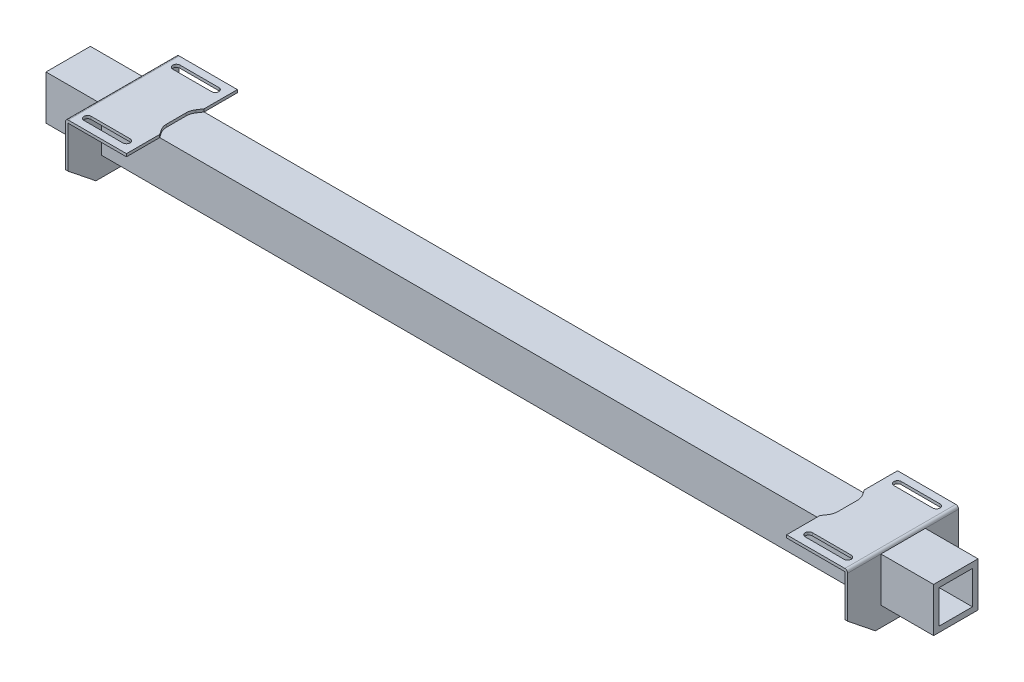
SolidWorks part; units mm, degrees
ref_plane "Front Plane" through (0, 0, 0) normal (0, 0, 1) x (1, 0, 0)
ref_plane "Top Plane" through (0, 0, 0) normal (0, 1, 0) x (1, 0, 0)
ref_plane "Right Plane" through (0, 0, 0) normal (1, 0, 0) x (0, 0, -1)
sketch "Sketch3" plane through (0, 0, 0) normal (1, 0, 0) x (0, 0, -1)
  line L1 (0, 0) -> (80, 0)
  line L2 (0, 0) -> (0, 80)
  line L3 (0, 80) -> (80, 80)
  line L4 (80, 0) -> (80, 80)
  line L5 (10, 70) -> (70, 70)
  line L6 (10, 70) -> (10, 10)
  line L7 (10, 10) -> (70, 10)
  line L8 (70, 70) -> (70, 10)
  dimension "D1" = 80
  dimension "D2" = 80
  dimension "D3" = 10
  dimension "D4" = 10
  dimension "D5" = 10
  dimension "D6" = 10
extrude "Boss-Extrude2" add sketch "Sketch3" along normal blind 1600
ref_plane "Plane1" through (1500, 0, 0) normal (1, 0, 0) x (0, 0, -1)
sketch "Sketch7" plane through (1500, 0, 0) normal (1, 0, 0) x (0, 0, -1)
  line L0 (-60, 85) -> (140, 85)
  line L1 (140, 85) -> (140, 5)
  line L2 (140, 5) -> (90, -35)
  line L3 (90, -35) -> (-10, -35)
  line L4 (-10, -35) -> (-60, 5)
  line L5 (-60, 5) -> (-60, 85)
  line L6 (80, 80) -> (0, 80) construction
  line L7 (70, 70) -> (10, 70) construction
  line L8 (70, 70) -> (10, 70)
  line L9 (70, 10) -> (70, 70) construction
  line L10 (10, 10) -> (70, 10) construction
  line L11 (10, 70) -> (10, 10) construction
  line L12 (70, 10) -> (70, 70)
  line L13 (10, 10) -> (70, 10)
  line L14 (10, 70) -> (10, 10)
  point P10 (40, 85)
  point P11 (40, 80)
  dimension "D1" = 200
  dimension "D2" = 120
  dimension "D3" = 50
  dimension "D4" = 50
  dimension "D5" = 5
  dimension "D6" = 40
extrude "Boss-Extrude3" add sketch "Sketch7" along normal blind 5
sketch "Sketch8" plane through (0, 0, -80) normal (0, 0, -1) x (-1, 0, 0)
  line L0 (-1505, 85) -> (-1500, 85) construction
  line L1 (-1505, 85) -> (-1395, 85)
  line L2 (-1505, 85) -> (-1505, 80)
  line L3 (-1505, 80) -> (-1395, 80)
  line L4 (-1395, 85) -> (-1395, 80)
  line L5 (-1505, 5) -> (-1505, 85) construction
  dimension "D1" = 5
  dimension "D2" = 110
extrude "Boss-Extrude4" add sketch "Sketch8" along normal up to surface and the other way up to surface up to face at (1502.5, 45, -140) other way up to face at (1502.5, 45, 60)
sketch "Sketch9" plane through (0, 85, 0) normal (0, 1, 0) x (1, 0, 0)
  line L0 (1395, 80) -> (1400.8013, 71.2981)
  line L1 (1395, 140) -> (1395, -60) construction
  line L2 (1405, 57.4306) -> (1405, 22.5694)
  line L3 (1400.8013, 8.7019) -> (1395, 0)
  line L4 (1395, 0) -> (0, 0) construction
  line L5 (1395, 0) -> (1395, 80)
  line L6 (1600, 80) -> (1600, 0) construction
  arc A0 (1405, 22.5694) -> (1400.8013, 8.7019) centre (1380, 22.5694) cw
  arc A1 (1400.8013, 71.2981) -> (1405, 57.4306) centre (1380, 57.4306) cw
  point P15 (1405, 15)
  point P18 (1405, 65)
  dimension "D4" = 25
  dimension "D1" = 10
  dimension "D2" = 15
  dimension "D3" = 15
extrude "Cut-Extrude1" cut sketch "Sketch9" against normal up to surface (5 mm away) up to face at (1447.5, 80, 30)
sketch "Sketch10" plane through (0, 85, 0) normal (0, 1, 0) x (1, 0, 0)
  line L0 (1415, 120) -> (1485, 120) construction
  line L1 (1415, 126.5) -> (1485, 126.5)
  line L2 (1415, 113.5) -> (1485, 113.5)
  line L3 (1415, -40) -> (1485, -40) construction
  line L4 (1415, -33.5) -> (1485, -33.5)
  line L5 (1415, -46.5) -> (1485, -46.5)
  line L6 (1505, 140) -> (1395, 140) construction
  arc A0 (1415, 126.5) -> (1415, 113.5) centre (1415, 120) ccw
  arc A1 (1485, 113.5) -> (1485, 126.5) centre (1485, 120) ccw
  arc A2 (1415, -33.5) -> (1415, -46.5) centre (1415, -40) ccw
  arc A3 (1485, -46.5) -> (1485, -33.5) centre (1485, -40) ccw
  point P2 (1450, 120)
  point P7 (1450, -40)
  point P16 (1450, 140)
  point P17 (1450, 126.5)
  dimension "D1" = 70
  dimension "D2" = 13
  dimension "D3" = 13
  dimension "D4" = 160
  dimension "D5" = 20
extrude "Cut-Extrude2" cut sketch "Sketch10" against normal up to next
fillet "Fillet1" radius 5 1 edges at (1505, 85, -40)
ref_plane "Plane2" through (800, 0, 0) normal (1, 0, 0) x (0, 0, -1)
mirror "Mirror1" about plane through (800, 0, 0) normal (1, 0, 0) of "Fillet1", "Boss-Extrude3"
mirror "Mirror2" about plane through (800, 0, 0) normal (1, 0, 0) of "Fillet1", "Cut-Extrude2", "Boss-Extrude3", "Boss-Extrude4", "Cut-Extrude1"
sketch "Sketch13" plane through (0, 0, 0) normal (0, 0, 1) x (1, 0, 0)
  line L0 (0, 40) -> (2446.8223, 40) construction
  line L1 (0, 80) -> (0, 0) construction
sketch "Sketch14" plane through (0, 80, 0) normal (0, 1, 0) x (1, 0, 0)
  line L0 (800, 80) -> (800, 0) construction
  line L1 (1500, 80) -> (100, 80) construction
  line L2 (1500, 0) -> (100, 0) construction
  line L3 (706.4267, 40) -> (893.5733, 40) construction
  point P8 (800, 40)
equation "\"D2@Sketch3\"=\"D1@Sketch3\""
equation "\"D4@Sketch3\"=\"D3@Sketch3\""
equation "\"D5@Sketch3\"=\"D3@Sketch3\""
equation "\"D6@Sketch3\"=\"D3@Sketch3\""
equation "\"D3@Sketch9\"=\"D2@Sketch9\""
